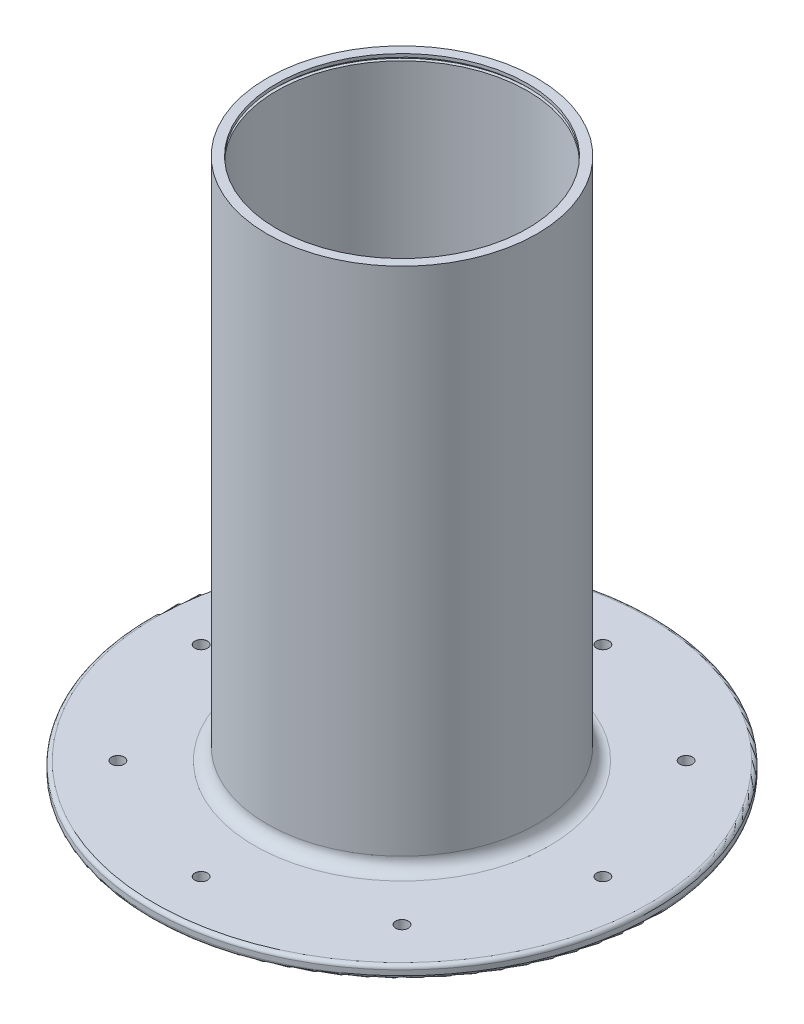
SolidWorks part; units mm, degrees
note: The reader was unsure of these and kept them because the rebuilt part matched: shared geometry of "Sketch1<3>", "Sketch1<5>".
material "1.0503 (C45)"
ref_plane "Front Plane" through (0, 0, 0) normal (0, 0, 1) x (1, 0, 0)
ref_plane "Top Plane" through (0, 0, 0) normal (0, 1, 0) x (1, 0, 0)
ref_plane "Right Plane" through (0, 0, 0) normal (1, 0, 0) x (0, 0, -1)
sketch "Sketch1" plane through (0, 0, 0) normal (0, 1, 0) x (1, 0, 0)
  circle A0 centre (0, 0) radius 100
  circle A1 centre (0, 0) radius 107.5
  circle A2 centre (0, 0) radius 95
  circle A3 centre (0, 0) radius 31
  point P0 (0, 0)
  dimension "D1" = 200
  dimension "D2" = 215
  dimension "D3" = 190
  dimension "D4" = 62
extrude "Boss-Extrude1" add sketch "Sketch1" along normal blind 155 and the other way blind 272 contours A1 A0
extrude "Boss-Extrude2" add sketch "Sketch1<3>" against normal blind 17 contours A0 A2 | A2 A3
sketch "Sketch1<3>" plane through (0, 0, 0) normal (0, 1, 0) x (1, 0, 0) same geometry as "Sketch1"
extrude "Cut-Extrude1" cut sketch "Sketch1<5>" against normal blind 4 contours A2 A3
sketch "Sketch1<5>" plane through (0, 0, 0) normal (0, 1, 0) x (1, 0, 0) same geometry as "Sketch1"
ref_plane "Plane1" through (0, -17, 0) normal (0, -1, 0) x (-1, 0, 0)
sketch "Sketch2" plane through (0, -17, 0) normal (0, -1, 0) x (-1, 0, 0)
  line L0 (0, 0) -> (0, 90.7247) construction
  point P0 (0, 0)
  point P4 (0, 70)
  point P5 (49.4975, 49.4975)
  point P8 (70, 0)
  point P9 (49.4975, -49.4975)
  point P10 (0, -70)
  point P11 (-49.4975, -49.4975)
  point P12 (-70, 0)
  point P13 (-49.4975, 49.4975)
  point P14 (0, 0)
  dimension "D1" = 70
  dimension "D2" = 8
hole_wizard "Ø4.0mm Dowel Hole1" positions "Sketch3" profile "Sketch4" hole size "Ø4.0" standard "ISO"
sketch "Sketch3" plane through (0, -17, 0) normal (0, -1, 0) x (-1, 0, 0)
  point P0 (0, 70)
  point P3 (49.4975, 49.4975)
  point P6 (-49.4975, 49.4975)
  point P9 (-70, 0)
  point P12 (-49.4975, -49.4975)
  point P15 (0, -70)
  point P18 (49.4975, -49.4975)
  point P21 (70, 0)
sketch "Sketch4" plane through (0, -17, -70) normal (1, 0, 0) x (0, 0, -1)
  line L0 (0, 0) -> (0, 14.2007)
  line L1 (0, 14.2007) -> (2, 12.999)
  line L2 (2, 12.999) -> (2, 0.025)
  line L3 (2, 0.025) -> (2.025, 0)
  line L5 (2.025, 0) -> (0, 0)
  line L6 (-2, 0.025) -> (-2.025, 0) construction
  line L10 (0, 14.2007) -> (-2, 12.999) construction
  line L11 (0, -6.35) -> (0, 107.95) construction
  dimension "Hole Dia." = 4
  dimension "Hole Depth" = 12.999
  dimension "Near C'Sink Dia." = 4.05
  dimension "Near C'Sink Angle" = 90
  dimension "Drill Angle" = 118
ref_plane "Plane2" through (0, -4, 0) normal (0, 1, 0) x (1, 0, 0)
sketch "Sketch5" plane through (0, -4, 0) normal (0, 1, 0) x (1, 0, 0)
  line L0 (0, 0) -> (0, 90.7247) construction
  line L1 (46.3948, 46.3948) -> (50.6331, 45.2591)
  line L2 (0, 65.6121) -> (3.8, 67.8061)
  line L3 (3.8, 67.8061) -> (3.8, 72.1939)
  line L4 (3.8, 72.1939) -> (0, 74.3879)
  line L5 (0, 74.3879) -> (-3.8, 72.1939)
  line L6 (-3.8, 72.1939) -> (-3.8, 67.8061)
  line L7 (-3.8, 67.8061) -> (0, 65.6121)
  line L8 (50.6331, 45.2591) -> (53.7358, 48.3618)
  line L9 (53.7358, 48.3618) -> (52.6002, 52.6002)
  line L10 (52.6002, 52.6002) -> (48.3618, 53.7358)
  line L11 (48.3618, 53.7358) -> (45.2591, 50.6331)
  line L12 (45.2591, 50.6331) -> (46.3948, 46.3948)
  line L13 (65.6121, 0) -> (67.8061, -3.8)
  line L14 (67.8061, -3.8) -> (72.1939, -3.8)
  line L15 (72.1939, -3.8) -> (74.3879, 0)
  line L16 (74.3879, 0) -> (72.1939, 3.8)
  line L17 (72.1939, 3.8) -> (67.8061, 3.8)
  line L18 (67.8061, 3.8) -> (65.6121, 0)
  line L19 (46.3948, -46.3948) -> (45.2591, -50.6331)
  line L20 (45.2591, -50.6331) -> (48.3618, -53.7358)
  line L21 (48.3618, -53.7358) -> (52.6002, -52.6002)
  line L22 (52.6002, -52.6002) -> (53.7358, -48.3618)
  line L23 (53.7358, -48.3618) -> (50.6331, -45.2591)
  line L24 (50.6331, -45.2591) -> (46.3948, -46.3948)
  line L25 (0, -65.6121) -> (-3.8, -67.8061)
  line L26 (-3.8, -67.8061) -> (-3.8, -72.1939)
  line L27 (-3.8, -72.1939) -> (0, -74.3879)
  line L28 (0, -74.3879) -> (3.8, -72.1939)
  line L29 (3.8, -72.1939) -> (3.8, -67.8061)
  line L30 (3.8, -67.8061) -> (0, -65.6121)
  line L31 (-46.3948, -46.3948) -> (-50.6331, -45.2591)
  line L32 (-50.6331, -45.2591) -> (-53.7358, -48.3618)
  line L33 (-53.7358, -48.3618) -> (-52.6002, -52.6002)
  line L34 (-52.6002, -52.6002) -> (-48.3618, -53.7358)
  line L35 (-48.3618, -53.7358) -> (-45.2591, -50.6331)
  line L36 (-45.2591, -50.6331) -> (-46.3948, -46.3948)
  line L37 (-65.6121, 0) -> (-67.8061, 3.8)
  line L38 (-67.8061, 3.8) -> (-72.1939, 3.8)
  line L39 (-72.1939, 3.8) -> (-74.3879, 0)
  line L40 (-74.3879, 0) -> (-72.1939, -3.8)
  line L41 (-72.1939, -3.8) -> (-67.8061, -3.8)
  line L42 (-67.8061, -3.8) -> (-65.6121, 0)
  line L43 (-46.3948, 46.3948) -> (-45.2591, 50.6331)
  line L44 (-45.2591, 50.6331) -> (-48.3618, 53.7358)
  line L45 (-48.3618, 53.7358) -> (-52.6002, 52.6002)
  line L46 (-52.6002, 52.6002) -> (-53.7358, 48.3618)
  line L47 (-53.7358, 48.3618) -> (-50.6331, 45.2591)
  line L48 (-50.6331, 45.2591) -> (-46.3948, 46.3948)
  circle A0 centre (0, 70) radius 3.8 construction
  point P0 (0, 0)
  point P4 (0, 70)
  point P5 (49.4975, 49.4975)
  point P8 (70, 0)
  point P9 (49.4975, -49.4975)
  point P10 (0, -70)
  point P11 (-49.4975, -49.4975)
  point P12 (-70, 0)
  point P13 (-49.4975, 49.4975)
  point P14 (0, 0)
  point P67 (0, 0)
  dimension "D1" = 70
  dimension "D2" = 8
  dimension "D3" = 8
extrude "Cut-Extrude2" cut sketch "Sketch5" against normal blind 5
ref_plane "Plane3" through (0, -272, 0) normal (0, -1, 0) x (-1, 0, 0)
sketch "Sketch8" plane through (0, -272, 0) normal (0, -1, 0) x (-1, 0, 0)
  line L0 (0, 0) -> (0, 81.9785) construction
  circle A0 centre (0, 0) radius 200
  circle A1 centre (0, 0) radius 100
  point P3 (0, 160)
  point P4 (113.1371, 113.1371)
  point P7 (160, 0)
  point P8 (113.1371, -113.1371)
  point P9 (0, -160)
  point P10 (-113.1371, -113.1371)
  point P11 (-160, 0)
  point P12 (-113.1371, 113.1371)
  point P13 (0, 0)
  dimension "D3" = 200
  dimension "D4" = 400
  dimension "D1" = 160
  dimension "D2" = 8
extrude "Boss-Extrude3" add sketch "Sketch8" against normal blind 10
sketch "Sketch9" plane through (0, -272, 0) normal (0, -1, 0) x (-1, 0, 0)
  line L0 (0, 0) -> (0, 81.9785) construction
  circle A0 centre (0, 0) radius 200
  circle A1 centre (0, 0) radius 100
  point P3 (0, 160)
  point P4 (113.1371, 113.1371)
  point P7 (160, 0)
  point P8 (113.1371, -113.1371)
  point P9 (0, -160)
  point P10 (-113.1371, -113.1371)
  point P11 (-160, 0)
  point P12 (-113.1371, 113.1371)
  point P13 (0, 0)
  dimension "D3" = 200
  dimension "D4" = 400
  dimension "D1" = 160
  dimension "D2" = 8
hole_wizard "Ø10.0mm Dowel Hole1" positions "Sketch10" profile "Sketch11" hole size "Ø10.0" standard "ISO"
sketch "Sketch10" plane through (0, -262, 0) normal (0, 1, 0) x (1, 0, 0)
  point P0 (160, 0)
  point P3 (113.1371, 113.1371)
  point P6 (0, 160)
  point P9 (-113.1371, 113.1371)
  point P12 (-160, 0)
  point P15 (-113.1371, -113.1371)
  point P18 (113.1371, -113.1371)
  point P21 (0, -160)
sketch "Sketch11" plane through (160, -262, 0) normal (1, 0, 0) x (0, 0, 1)
  line L0 (0, 0) -> (0, 13.0033)
  line L1 (0, 13.0033) -> (5, 9.999)
  line L2 (5, 9.999) -> (5, 0.025)
  line L3 (5, 0.025) -> (5.025, 0)
  line L5 (5.025, 0) -> (0, 0)
  line L6 (-5, 0.025) -> (-5.025, 0) construction
  line L10 (0, 13.0033) -> (-5, 9.999) construction
  line L11 (0, -6.35) -> (0, 107.95) construction
  dimension "Hole Dia." = 10
  dimension "Hole Depth" = 9.999
  dimension "Near C'Sink Dia." = 10.05
  dimension "Near C'Sink Angle" = 90
  dimension "Drill Angle" = 118
ref_plane "Plane4" through (0, 150, 0) normal (0, 1, 0) x (1, 0, 0)
sketch "Sketch12" plane through (0, 150, 0) normal (0, 1, 0) x (1, 0, 0)
  circle A0 centre (0, 0) radius 102.5
  dimension "D1" = 205
extrude "Cut-Extrude3" cut sketch "Sketch12" along normal blind 2.5
fillet "Fillet1" radius 10 3 edges at (0, -272, 100) (0, -262, -107.5) (0, -17, 100)
fillet "Fillet2" radius 3 2 edges at (0, -262, -200) (0, -272, -200)
fillet "Fillet3" radius 1 2 edges at (0, 0, 100) (0, -4, 95)
